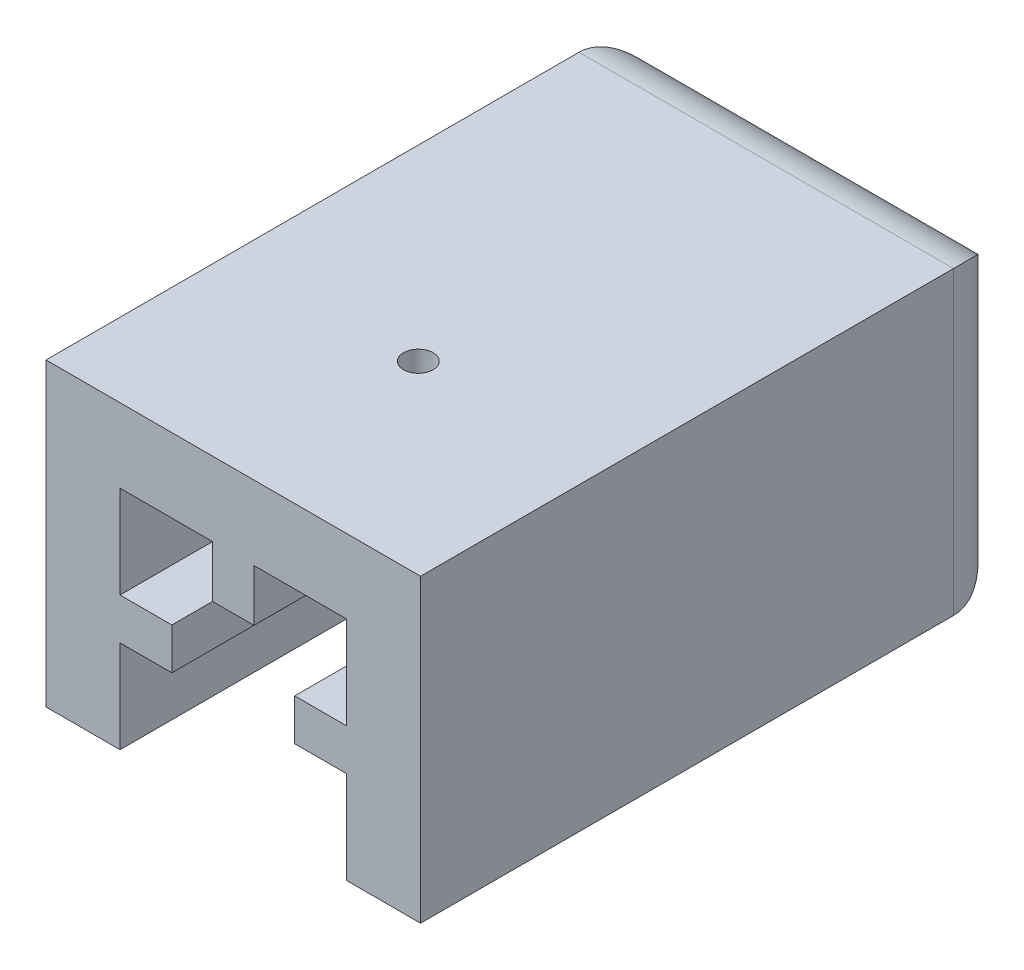
SolidWorks part; units mm, degrees
ref_plane "Plano frontal" through (0, 0, 0) normal (0, 0, 1) x (1, 0, 0)
ref_plane "Plano superior" through (0, 0, 0) normal (0, 1, 0) x (1, 0, 0)
ref_plane "Plano direito" through (0, 0, 0) normal (1, 0, 0) x (0, 0, -1)
sketch "Esboço1" plane through (0, 0, 0) normal (0, 0, 1) x (1, 0, 0)
  line L0 (-7.65, 0) -> (-12.65, 0)
  line L1 (-12.65, 0) -> (-12.65, 20.3)
  line L2 (-12.65, 20.3) -> (12.65, 20.3)
  line L3 (0, 20.3) -> (0, 15.3) construction
  line L4 (7.65, 15.3) -> (-7.65, 15.3)
  line L5 (-7.65, 15.3) -> (-7.65, 0)
  line L6 (0, 0) -> (0, 23.1347) construction
  line L7 (7.65, 15.3) -> (7.65, 0)
  line L8 (12.65, 0) -> (12.65, 20.3)
  line L9 (7.65, 0) -> (12.65, 0)
  dimension "D1" = 15.3
  dimension "D2" = 15.3
  dimension "D3" = 5
extrude "Ressalto-extrusão1" add sketch "Esboço1" along normal blind 20
sketch "Esboço2" plane through (0, 0, 0) normal (0, 0, -1) x (-1, 0, 0)
  line L0 (-7.65, 15.3) -> (7.65, 0) construction
  line L1 (-12.65, 20.3) -> (12.65, 20.3)
  line L2 (-12.65, 20.3) -> (-12.65, 0)
  line L3 (-12.65, 0) -> (12.65, 0)
  line L4 (12.65, 20.3) -> (12.65, 0)
  line L5 (-3.85, 7.65) -> (-3.85, 0)
  line L6 (3.85, 7.65) -> (3.85, 0)
  circle A0 centre (0, 7.65) radius 3.85
  dimension "D1" = 7.7
extrude "Ressalto-extrusão2" add sketch "Esboço2" along normal blind 20 contours L2 L3 L4 L1 | A0
extrude "Corte-extrusão1" cut sketch "Esboço2<3>" along normal blind 10 contours L0 A0 L5 L3 L6 | A0 L0 L6 region at (-3.503, 5.173, 0) region at (0.1637, 2.263, 0)
sketch "Esboço2<3>" plane through (0, 0, 0) normal (0, 0, -1) x (-1, 0, 0) same geometry as "Esboço2"
sketch "Esboço3" plane through (0, 0, 20) normal (0, 0, 1) x (1, 0, 0)
  line L0 (0, 0) -> (0, 15.3) construction
  line L1 (-7.65, 15.3) -> (7.65, 15.3) construction
  line L2 (7.65, 9.05) -> (4.15, 9.05)
  line L3 (7.65, 15.3) -> (7.65, 0) construction
  line L4 (4.15, 9.05) -> (4.15, 6.25)
  line L5 (4.15, 6.25) -> (7.65, 6.25)
  line L6 (0, 7.65) -> (3.85, 7.65) construction
  line L7 (-4.15, 6.25) -> (-7.65, 6.25)
  line L8 (-4.15, 9.05) -> (-4.15, 6.25)
  line L9 (-7.65, 9.05) -> (-4.15, 9.05)
  line L10 (-1.4, 15.3) -> (-1.4, 11.8)
  line L11 (-1.4, 11.8) -> (1.4, 11.8)
  line L12 (1.4, 11.8) -> (1.4, 15.3)
  line L13 (-1.4, 15.3) -> (1.4, 15.3)
  line L14 (7.65, 9.05) -> (7.65, 6.25)
  line L15 (-7.65, 9.05) -> (-7.65, 6.25)
  dimension "D1" = 3.5
  dimension "D2" = 2.8
extrude "Ressalto-extrusão3" add sketch "Esboço3" against normal offset from surface (17 mm away) 3 up to face at (0, 6.2188, 0)
sketch "Esboço4" plane through (0, 15.3, 0) normal (0, -1, 0) x (1, 0, 0)
  circle A0 centre (0, 7.5) radius 1
  dimension "D2" = 2
  dimension "D1" = 7.5
extrude "Corte-extrusão2" cut sketch "Esboço4" against normal through all both and the other way through all
fillet "Filete1" radius 4 4 edges at (-12.65, 10.15, -20) (0, 20.3, -20) (0, 0, -20) (12.65, 10.15, -20)
equation "\"D2@Esboço1\"=\"D1@Esboço1\""
